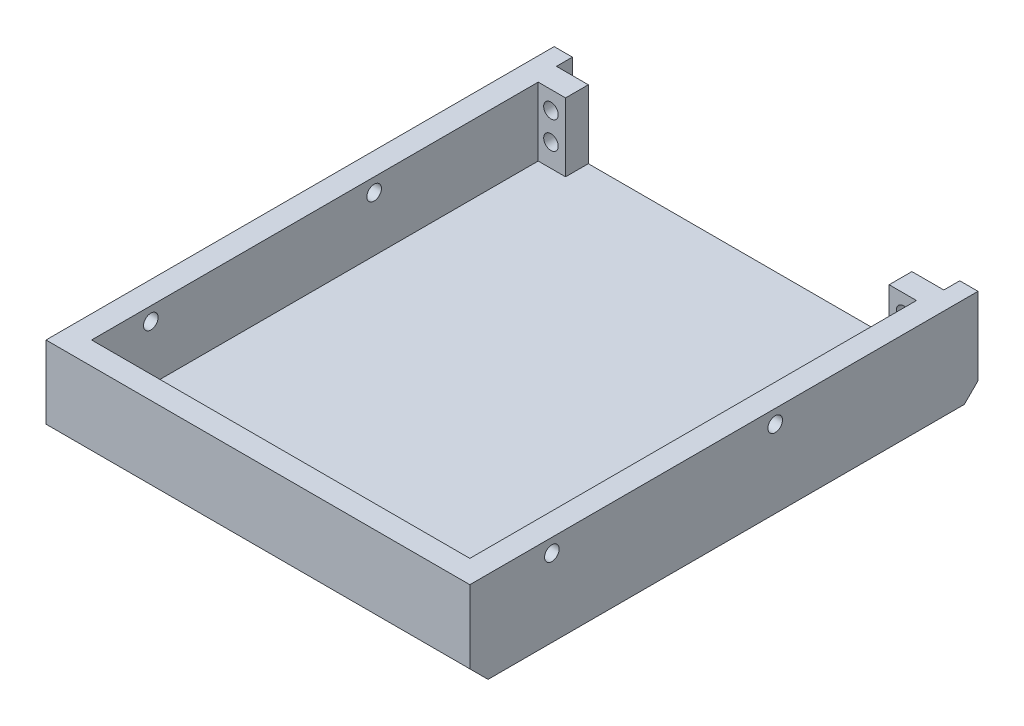
SolidWorks part; units mm, degrees
ref_plane "Alzado" through (0, 0, 0) normal (0, 0, 1) x (1, 0, 0)
ref_plane "Planta" through (0, 0, 0) normal (0, 1, 0) x (1, 0, 0)
ref_plane "Vista lateral" through (0, 0, 0) normal (1, 0, 0) x (0, 0, -1)
sketch "Croquis1" plane through (0, 0, 0) normal (0, 1, 0) x (1, 0, 0)
  line L1 (-46.5, -54) -> (46.5, -54)
  line L2 (-46.5, -54) -> (-46.5, 54)
  line L3 (-46.5, 54) -> (46.5, 54)
  line L4 (46.5, -54) -> (46.5, 54)
  line L5 (-46.5, -54) -> (46.5, 54) construction
  line L6 (-46.5, 54) -> (46.5, -54) construction
  point P0 (0, 0)
  dimension "D1" = 108
  dimension "D2" = 93
extrude "Saliente-Extruir1" add sketch "Croquis1" along normal blind 20
shell "Vaciado1" thickness 5 removed face at (0, 20, 0)
sketch "Croquis3" plane through (-46.5, 0, 0) normal (-1, 0, 0) x (0, 0, 1)
  line L0 (36, 17) -> (-13, 17) construction
  line L1 (54, 20) -> (54, 0) construction
  line L2 (-54, 20) -> (54, 20) construction
  circle A0 centre (36, 17) radius 1.6
  circle A1 centre (-13, 17) radius 1.6
  dimension "D1" = 3.2
  dimension "D2" = 3.2
  dimension "D3" = 49
  dimension "D4" = 18
  dimension "D5" = 3
extrude "Cortar-Extruir1" cut sketch "Croquis3" against normal blind 93
sketch "Croquis4" plane through (0, 0, -54) normal (0, 0, -1) x (-1, 0, 0)
  line L0 (-46.5, 20) -> (46.5, 20) construction
  line L1 (-41.5, 20) -> (41.5, 20)
  line L2 (-41.5, 20) -> (-41.5, 5)
  line L3 (-41.5, 5) -> (41.5, 5)
  line L4 (41.5, 20) -> (41.5, 5)
  line L5 (-46.5, 0) -> (46.5, 0) construction
  line L6 (46.5, 20) -> (46.5, 0) construction
  line L7 (-46.5, 20) -> (-46.5, 0) construction
  dimension "D1" = 5
  dimension "D2" = 5
  dimension "D3" = 5
extrude "Cortar-Extruir2" cut sketch "Croquis4" against normal blind 5
sketch "Croquis5" plane through (-41.5, 0, 0) normal (1, 0, 0) x (0, 0, -1)
  line L0 (-54, 20) -> (54, 20) construction
  line L1 (49, 20) -> (54, 20)
  line L2 (49, 20) -> (49, 5)
  line L3 (49, 5) -> (54, 5)
  line L4 (54, 20) -> (54, 5)
  dimension "D1" = 5
extrude "Saliente-Extruir2" add sketch "Croquis5" along normal blind 6
mirror "Simetría1" about plane through (0, 0, 0) normal (1, 0, 0) of "Saliente-Extruir2"
sketch "Croquis6" plane through (0, 0, -54) normal (0, 0, -1) x (-1, 0, 0)
  line L0 (-38.7, 16) -> (-38.7, 10) construction
  line L1 (-46.5, 20) -> (-35.5, 20) construction
  line L2 (-35.5, 5) -> (-35.5, 20) construction
  circle A0 centre (-38.7, 16) radius 1.6
  circle A1 centre (-38.7, 10) radius 1.6
  dimension "D1" = 3.2
  dimension "D2" = 3.2
  dimension "D3" = 4
  dimension "D4" = 6
  dimension "D5" = 3.2
extrude "Cortar-Extruir3" cut sketch "Croquis6" against normal up to next
mirror "Simetría2" about plane through (0, 0, 0) normal (1, 0, 0) of "Cortar-Extruir3"
sketch "Croquis7" plane through (0, 0, 0) normal (0, 1, 0) x (1, 0, 0)
  line L0 (35, 57.5) -> (31, 57.5) construction
  line L1 (46.5, 57.5) -> (42.5, 57.5)
  line L2 (46.5, 57.5) -> (46.5, 54)
  line L3 (46.5, 54) -> (42.5, 54)
  line L4 (42.5, 57.5) -> (42.5, 54)
  dimension "D1" = 4
extrude "Saliente-Extruir3" add sketch "Croquis7" along normal up to surface (20 mm away) up to face at (0, 20, -17.1667)
chamfer "Chaflán1" distance 3 angle 45 1 edges at (44.5, 0, -57.5)
mirror "Simetría3" about plane through (0, 0, 0) normal (1, 0, 0) of "Chaflán1", "Saliente-Extruir3"
chamfer "Chaflán2" distance 4 angle 45 1 edges at (0, 0, 54)
